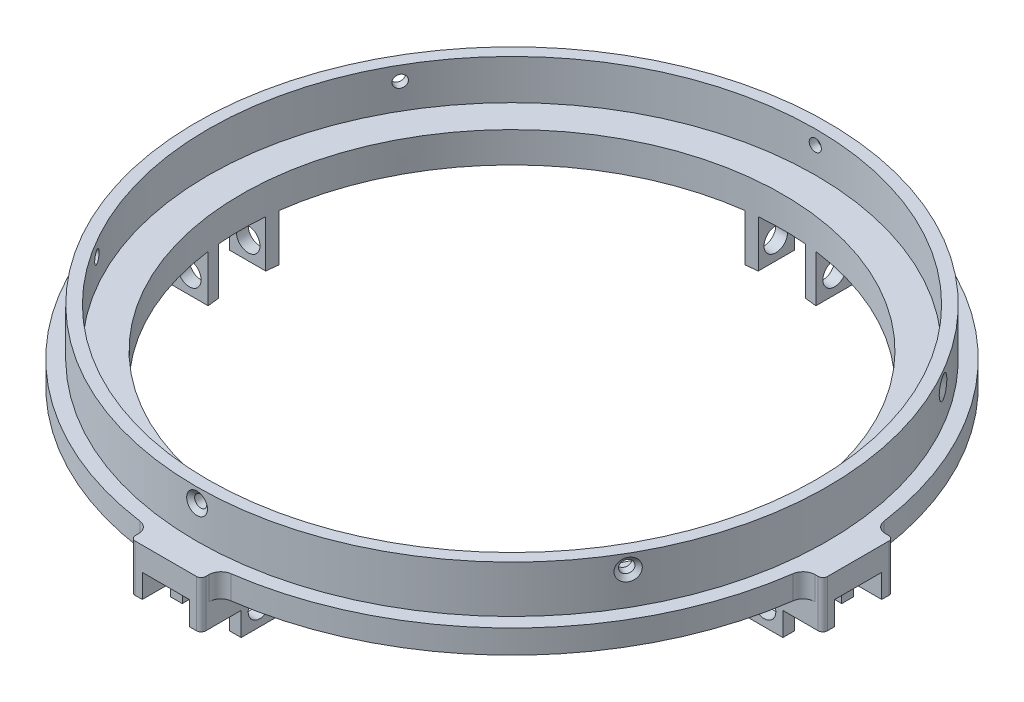
SolidWorks part; units mm, degrees
material "ASTM A36 Steel"
ref_plane "Front" through (0, 0, 0) normal (0, 0, 1) x (1, 0, 0)
ref_plane "Top" through (0, 0, 0) normal (0, 1, 0) x (1, 0, 0)
ref_plane "Right" through (0, 0, 0) normal (1, 0, 0) x (0, 0, -1)
sketch "Sketch1" plane through (0, 0, 0) normal (0, 1, 0) x (1, 0, 0)
  line L1 (-152.4, 152.4) -> (152.4, 152.4)
  line L2 (-152.4, 152.4) -> (-152.4, -152.4)
  line L3 (-152.4, -152.4) -> (152.4, -152.4)
  line L4 (152.4, 152.4) -> (152.4, -152.4)
  line L5 (-152.4, 152.4) -> (152.4, -152.4) construction
  line L6 (-152.4, -152.4) -> (152.4, 152.4) construction
  point P0 (0, 0)
  dimension "D1" = 304.8
  dimension "D2" = 304.8
extrude "Boss-Extrude1" add sketch "Sketch1" along normal blind 19.05
sketch "Sketch2" plane through (0, 19.05, 0) normal (0, 1, 0) x (1, 0, 0)
  circle A0 centre (0, 0) radius 81.915
  dimension "D1" = 163.83
extrude "Cut-Extrude1" cut sketch "Sketch2" against normal blind 10.795
sketch "Sketch3" plane through (0, 8.255, 0) normal (0, 1, 0) x (1, 0, 0)
  circle A0 centre (0, 0) radius 73.025
  dimension "D1" = 146.05
extrude "Cut-Extrude2" cut sketch "Sketch3" against normal up to next
sketch "Sketch4" plane through (0, 19.05, 0) normal (0, 1, 0) x (1, 0, 0)
  circle A0 centre (0, 0) radius 85.09
  dimension "D1" = 170.18
extrude "Cut-Extrude4" cut sketch "Sketch4" against normal blind 12.7 flip side to cut
hole_wizard "CSK for #4 Flat Head Machine Screw (100)1" positions "3DSketch6" profile "Sketch10" countersink size "#4" standard "ANSI Inch" end condition up to next
sketch3d "3DSketch6"
  point P0 (0.1296, 15.24, 85.0899)
  dimension "D1" = 3.81
sketch "Sketch10" plane through (0.1296, 15.24, 85.0899) normal (0, 1, 0) x (1, 0, -0.0015)
  line L0 (0, 0) -> (0, 197.0349)
  line L1 (0, 197.0349) -> (1.6319, 197.0349)
  line L2 (1.6319, 197.0349) -> (1.6319, 1.0284)
  line L3 (1.6319, 1.0284) -> (2.8575, 0)
  line L5 (2.8575, 0) -> (0, 0)
  line L6 (-1.6319, 1.0284) -> (-2.8575, 0) construction
  line L11 (0, -6.35) -> (0, 107.95) construction
  dimension "Thru Hole Dia." = 3.2639
  dimension "Thru Hole Depth" = 197.0349
  dimension "Near C'Sink Dia." = 5.715
  dimension "Near C'Sink Angle" = 100
pattern_circular "CirPattern1" count 6 over 360 about axis through (0, 19.05, 0) along (0, 1, 0) of "CSK for #4 Flat Head Machine Screw (100)1"
sketch "Sketch11" plane through (0, 6.35, 0) normal (0, 1, 0) x (1, 0, 0)
  line L0 (-91.1949, 9.525) -> (-92.075, 9.525)
  line L1 (0, 0) -> (0, 88.9) construction
  line L2 (-93.345, 8.255) -> (-93.345, -8.255)
  line L3 (-92.075, -9.525) -> (-91.1949, -9.525)
  line L4 (9.525, 91.1949) -> (9.525, 92.075)
  line L5 (8.255, 93.345) -> (-8.255, 93.345)
  line L6 (-9.525, 92.075) -> (-9.525, 91.1949)
  line L7 (0, 0) -> (88.9, 0) construction
  line L8 (88.9, 0) -> (93.345, 0) construction
  line L9 (-9.525, -91.1949) -> (-9.525, -92.075)
  line L10 (-8.255, -93.345) -> (8.255, -93.345)
  line L11 (9.525, -92.075) -> (9.525, -91.1949)
  line L12 (0, 0) -> (0, -88.9) construction
  line L13 (0, -88.9) -> (0, -93.345) construction
  line L14 (91.1949, -9.525) -> (92.075, -9.525)
  line L15 (93.345, -8.255) -> (93.345, 8.255)
  line L16 (0, 88.9) -> (0, 93.345) construction
  line L17 (92.075, 9.525) -> (91.1949, 9.525)
  line L18 (0, 0) -> (-88.9, 0) construction
  line L19 (-88.9, 0) -> (-93.345, 0) construction
  circle A0 centre (0, 0) radius 85.09 construction
  arc A1 (-91.1949, 9.525) -> (-88.0503, 12.2621) centre (-91.1949, 12.7) ccw
  arc A2 (-92.075, 9.525) -> (-93.345, 8.255) centre (-92.075, 8.255) ccw
  arc A3 (-93.345, -8.255) -> (-92.075, -9.525) centre (-92.075, -8.255) ccw
  arc A4 (-91.1949, -9.525) -> (-88.0503, -12.2621) centre (-91.1949, -12.7) cw
  arc A5 (9.525, 91.1949) -> (12.2621, 88.0503) centre (12.7, 91.1949) ccw
  arc A6 (8.255, -93.345) -> (9.525, -92.075) centre (8.255, -92.075) ccw
  arc A7 (9.525, 92.075) -> (8.255, 93.345) centre (8.255, 92.075) ccw
  arc A8 (-8.255, 93.345) -> (-9.525, 92.075) centre (-8.255, 92.075) ccw
  arc A9 (-9.525, 91.1949) -> (-12.2621, 88.0503) centre (-12.7, 91.1949) cw
  circle A10 centre (0, 0) radius 73.025 construction
  arc A11 (9.525, -91.1949) -> (12.2621, -88.0503) centre (12.7, -91.1949) cw
  arc A12 (-9.525, -91.1949) -> (-12.2621, -88.0503) centre (-12.7, -91.1949) ccw
  arc A13 (-9.525, -92.075) -> (-8.255, -93.345) centre (-8.255, -92.075) ccw
  arc A14 (91.1949, -9.525) -> (88.0503, -12.2621) centre (91.1949, -12.7) ccw
  arc A15 (92.075, -9.525) -> (93.345, -8.255) centre (92.075, -8.255) ccw
  arc A16 (93.345, 8.255) -> (92.075, 9.525) centre (92.075, 8.255) ccw
  circle A17 centre (0, 0) radius 88.9
  arc A18 (91.1949, 9.525) -> (88.0503, 12.2621) centre (91.1949, 12.7) cw
  circle A22 centre (0, 0) radius 79.375 construction
  circle A23 centre (0, 0) radius 98.425 construction
  point P1 (0, 73.025)
  point P50 (0, 0)
  point P69 (0, 0)
  point P72 (0, 0)
  circle M1 centre (0, 0) radius 85.09
  line M2 (152.4, -152.4) -> (152.4, 152.4)
  line M3 (152.4, 152.4) -> (-152.4, 152.4)
  line M4 (-152.4, 152.4) -> (-152.4, -152.4)
  line M5 (-152.4, -152.4) -> (152.4, -152.4)
  dimension "D1" = 3.175
  dimension "D4" = 1.27
  dimension "D7" = 177.8
  dimension "D8" = 4
  dimension "D5" = 158.75
  dimension "D9" = 19.05
  dimension "D2" = 0.8801
  dimension "D3" = 20.32
  dimension "D6" = 4
extrude "Cut-Extrude7" cut sketch "Sketch11" against normal blind 19.05 contours M5 M2 M3 M4 M1 region at (0, 6.35, 148.0895)
sketch "Sketch16" plane through (0, 0, 0) normal (0, 1, 0) x (1, 0, 0)
  line L1 (152.4, -152.4) -> (-152.4, -152.4) construction
  line L4 (-152.4, -152.4) -> (-152.4, 152.4) construction
  point P0 (0, 0)
  dimension "D1" = 304.8
  dimension "D2" = 304.8
  dimension "D3" = 152.4
  dimension "D4" = 152.4
sketch "Sketch18" plane through (0, 0, 0) normal (0, -1, 0) x (1, 0, 0)
  line L0 (0, 93.345) -> (0, 0) construction
  line L1 (-8.255, 93.345) -> (8.255, 93.345) construction
  line L2 (6.35, 72.7484) -> (-6.35, 72.7484) construction
  line L3 (6.35, 72.7484) -> (6.35, 93.345)
  line L4 (6.35, 93.345) -> (-6.35, 93.345) construction
  line L5 (-6.35, 72.7484) -> (-6.35, 93.345)
  line L6 (6.35, 72.7484) -> (-6.35, 93.345) construction
  line L7 (6.35, 93.345) -> (-6.35, 72.7484) construction
  line L8 (-9.525, 92.075) -> (-9.525, 72.4011)
  line L9 (-6.35, 93.345) -> (-8.255, 93.345)
  line L10 (9.525, 92.075) -> (9.525, 72.4011)
  line L11 (6.35, 93.345) -> (8.255, 93.345)
  line L12 (72.7484, -6.35) -> (93.345, -6.35)
  line L13 (72.7484, 6.35) -> (93.345, 6.35)
  line L14 (92.075, 9.525) -> (72.4011, 9.525)
  line L15 (93.345, 6.35) -> (93.345, 8.255)
  line L16 (92.075, -9.525) -> (72.4011, -9.525)
  line L17 (93.345, -6.35) -> (93.345, -8.255)
  line L18 (93.345, 0) -> (0, 0) construction
  line L19 (72.7484, -6.35) -> (72.7484, 6.35) construction
  line L20 (93.345, -6.35) -> (93.345, 6.35) construction
  line L21 (72.7484, -6.35) -> (93.345, 6.35) construction
  line L22 (93.345, -6.35) -> (72.7484, 6.35) construction
  line L23 (-6.35, -72.7484) -> (-6.35, -93.345)
  line L24 (6.35, -72.7484) -> (6.35, -93.345)
  line L25 (9.525, -92.075) -> (9.525, -72.4011)
  line L26 (6.35, -93.345) -> (8.255, -93.345)
  line L27 (-9.525, -92.075) -> (-9.525, -72.4011)
  line L28 (-6.35, -93.345) -> (-8.255, -93.345)
  line L29 (0, -93.345) -> (0, 0) construction
  line L30 (-6.35, -72.7484) -> (6.35, -72.7484) construction
  line L31 (-6.35, -93.345) -> (6.35, -93.345) construction
  line L32 (-6.35, -72.7484) -> (6.35, -93.345) construction
  line L33 (-6.35, -93.345) -> (6.35, -72.7484) construction
  line L34 (-72.7484, 6.35) -> (-93.345, 6.35)
  line L35 (-72.7484, -6.35) -> (-93.345, -6.35)
  line L36 (-92.075, -9.525) -> (-72.4011, -9.525)
  line L37 (-93.345, -6.35) -> (-93.345, -8.255)
  line L38 (-92.075, 9.525) -> (-72.4011, 9.525)
  line L39 (-93.345, 6.35) -> (-93.345, 8.255)
  line L40 (-93.345, 0) -> (0, 0) construction
  line L41 (-72.7484, 6.35) -> (-72.7484, -6.35) construction
  line L42 (-93.345, 6.35) -> (-93.345, -6.35) construction
  line L43 (-72.7484, 6.35) -> (-93.345, -6.35) construction
  line L44 (-93.345, 6.35) -> (-72.7484, -6.35) construction
  arc A0 (-6.35, 72.7484) -> (-9.525, 72.4011) centre (0, 0) ccw
  circle A1 centre (0, 0) radius 73.025 construction
  arc A2 (9.525, 72.4011) -> (6.35, 72.7484) centre (0, 0) ccw
  arc A3 (-9.525, 92.075) -> (-8.255, 93.345) centre (-8.255, 92.075) cw
  arc A4 (9.525, 92.075) -> (8.255, 93.345) centre (8.255, 92.075) ccw
  arc A5 (72.7484, 6.35) -> (72.4011, 9.525) centre (0, 0) ccw
  arc A6 (72.4011, -9.525) -> (72.7484, -6.35) centre (0, 0) ccw
  arc A7 (92.075, 9.525) -> (93.345, 8.255) centre (92.075, 8.255) cw
  arc A8 (92.075, -9.525) -> (93.345, -8.255) centre (92.075, -8.255) ccw
  arc A9 (6.35, -72.7484) -> (9.525, -72.4011) centre (0, 0) ccw
  arc A10 (-9.525, -72.4011) -> (-6.35, -72.7484) centre (0, 0) ccw
  arc A11 (9.525, -92.075) -> (8.255, -93.345) centre (8.255, -92.075) cw
  arc A12 (-9.525, -92.075) -> (-8.255, -93.345) centre (-8.255, -92.075) ccw
  arc A13 (-72.7484, -6.35) -> (-72.4011, -9.525) centre (0, 0) ccw
  arc A14 (-72.4011, 9.525) -> (-72.7484, 6.35) centre (0, 0) ccw
  arc A15 (-92.075, -9.525) -> (-93.345, -8.255) centre (-92.075, -8.255) cw
  arc A16 (-92.075, 9.525) -> (-93.345, 8.255) centre (-92.075, 8.255) ccw
  point P3 (0, 83.0467)
  point P25 (83.0467, 0)
  point P39 (0, -83.0467)
  point P53 (-83.0467, 0)
  point P66 (0, 0)
  dimension "D2" = 4
  dimension "D3" = 1.27
  dimension "D1" = 12.7
extrude "Boss-Extrude2" add sketch "Sketch18" along normal blind 12.7
sketch "Sketch19" plane through (9.525, 0, 0) normal (1, 0, 0) x (0, 0, -1)
  line L0 (-96.1332, -6.35) -> (-82.5611, -6.35)
  line L1 (-72.4011, 0) -> (-91.1949, 0) construction
  line L2 (-82.5611, -7.62) -> (-82.5611, -12.7)
  line L3 (-82.5611, -12.7) -> (-70.8041, -12.7)
  line L4 (-72.4011, -12.7) -> (-92.075, -12.7) construction
  line L5 (-82.5611, -7.62) -> (-82.5611, -6.35)
  line L7 (-70.8041, -12.7) -> (-70.8041, -20.3968)
  line L8 (-70.8041, -20.3968) -> (-96.1332, -20.3968)
  line L9 (-96.1332, -20.3968) -> (-96.1332, -6.35)
  line L10 (-72.4011, -12.7) -> (-72.4011, 0) construction
  arc A0 (-82.5611, -7.62) -> (-72.4011, -7.62) centre (-77.4811, -7.62) ccw construction
  dimension "D2" = 10.16
  dimension "D1" = 6.35
extrude "Cut-Extrude12" cut sketch "Sketch19" against normal blind 19.05
pattern_circular "CirPattern6" count 4 over 360 about axis through (0, 0, 0) along (0, -1, 0) of "Cut-Extrude12"
sketch "Sketch20" plane through (9.525, 0, 0) normal (1, 0, 0) x (0, 0, -1)
  line L0 (-72.4011, -12.7) -> (-72.4011, 0) construction
  line L1 (-72.4011, -12.7) -> (-82.5611, -12.7) construction
  circle A0 centre (-77.4811, -7.62) radius 5.08 construction
  circle A1 centre (-77.4811, -7.62) radius 3.175
  dimension "D1" = 10.16
  dimension "D2" = 6.35
extrude "Cut-Extrude13" cut sketch "Sketch20" against normal blind 19.05
pattern_circular "CirPattern7" count 4 over 360 about axis through (0, 19.05, 0) along (0, 1, 0) of "Cut-Extrude13"
